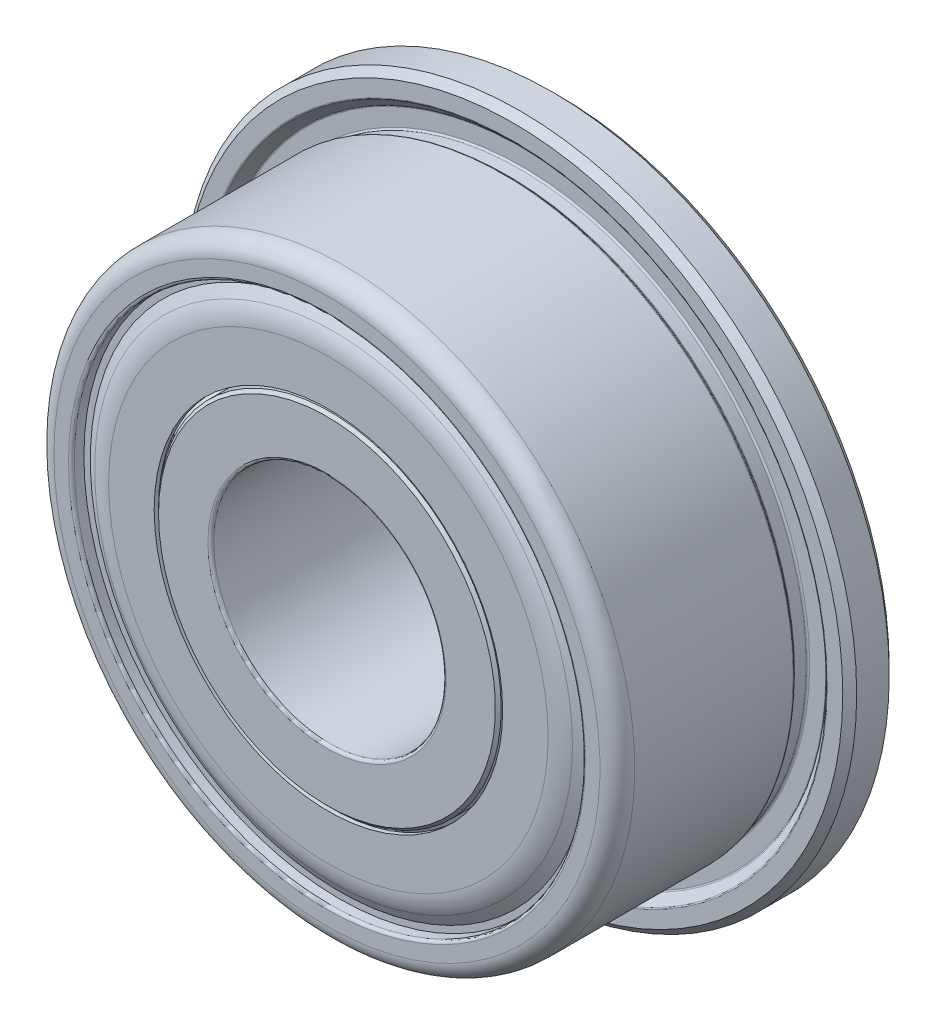
SolidWorks part; units mm, degrees
note: '?' marks a value the reader was unsure of.
ref_plane "Front Plane" through (0, 0, 0) normal (0, 0, 1) x (1, 0, 0)
ref_plane "Top Plane" through (0, 0, 0) normal (0, 1, 0) x (1, 0, 0)
ref_plane "Right Plane" through (0, 0, 0) normal (1, 0, 0) x (0, 0, -1)
sketch "Sketch1" plane through (0, 0, 0) normal (1, 0, 0) x (0, 0, -1)
  line L0 (-2, 0) -> (2, 0) construction
  line L1 (0, 5) -> (0, -5) construction
  line L2 (2, 5) -> (-2, 5)
  line L4 (-2, 5) -> (-2, 4.4)
  line L5 (-2, 4.4) -> (-0.78, 4.4)
  line L6 (2, 4.4) -> (0.78, 4.4)
  line L7 (2, 5) -> (2, 4.4)
  line L9 (0, 5) -> (0, 3.5) construction
  line L10 (0, 3.5) -> (0, 2) construction
  line L11 (-2, -4.4) -> (-2, 4.4) construction
  line L12 (1.2, -5.8) -> (2, -5.8)
  line L13 (1.2, -5.8) -> (1.2, 5.8)
  line L14 (1.2, 5.8) -> (2, 5.8)
  line L15 (2, -5.8) -> (2, 5.8)
  line L16 (1.2, -5.8) -> (2, 5.8) construction
  line L17 (1.2, 5.8) -> (2, -5.8) construction
  line L18 (-2, -2.95) -> (-2, 2.95)
  line L24 (0, -5) -> (-2, -5)
  line L25 (0, 2) -> (0, 5) construction
  line L26 (-2, 2.95) -> (-2, 2)
  line L27 (-2, 2) -> (2, 2)
  line L28 (2, 2) -> (2, 2.95)
  line L29 (2, 2.95) -> (0.58, 2.95)
  line L30 (-2, 2.95) -> (-0.58, 2.95)
  line L31 (-0.78, 4.4) -> (-0.78, 4.11)
  line L32 (-0.78, 4.11) -> (-0.58, 4.11)
  line L33 (0.78, 4.4) -> (0.78, 4.11)
  line L34 (0.78, 4.11) -> (0.58, 4.11)
  arc A3 (-0.58, 2.95) -> (0.58, 2.95) centre (0, 3.5) ccw
  circle A5 centre (0, 3.5247) radius 0.794
  arc A6 (-0.58, 4.11) -> (0.58, 4.11) centre (0, 3.5247) cw
  point P7 (-2, 4.4)
  point P13 (-1.9, 4.4)
  point P14 (0, 2)
  point P15 (1.6, 0)
  point P22 (2, 0)
  point P25 (-2, 0)
  point P27 (-2, 0)
  point P28 (-1.8, 4.4)
  point P29 (-1.7, 4.4)
  point P30 (-1.6, 4.4)
  point P31 (-1.5, 4.4)
  point P32 (-1.4, 4.4)
  point P33 (-1.3, 4.4)
  point P46 (0, 4.3487)
  point P50 (0, 2.7007)
  point P51 (0, 2.7307)
  point P52 (0, 4.3187)
  dimension "D3" = 1.588
  dimension "Shaft Dia" = 4
  dimension "Flange Thickness" = 0.8
  dimension "Flange OD" = 11.6
  dimension "D11" = 8.8
  dimension "D10" = 5.9
  dimension "Width" = 4
  dimension "OD" = 10
  dimension "D4" = 0.03
  dimension "D2" = 0.03
  dimension "D5" = 0.2
  dimension "D6" = 0.1
  dimension "D7" = 1.16
  dimension "D1" = 8
sketch "Sketch2" plane through (0, 0, 0) normal (0, 0, 1) x (1, 0, 0)
  line L0 (0, -2.95) -> (0, 2.95) construction
  circle A0 centre (0, 0) radius 2
  dimension "D1" = 4
sketch "Sketch3" plane through (0, 0, 0) normal (1, 0, 0) x (0, 0, -1)
  line L2 (-2, 5) -> (-2, 4.4) construction
  line L3 (2, 5) -> (-2, 5) construction
  line L4 (2, 5) -> (2, 4.4) construction
  line L5 (2, 4.4) -> (0.78, 4.4) construction
  line L6 (-2, 4.4) -> (-0.78, 4.4) construction
  line L13 (-2, 5) -> (-2, 4.4)
  line L21 (2, 5) -> (-2, 5)
  line L22 (2, 5) -> (2, 4.4)
  line L23 (2, 4.4) -> (0.78, 4.4)
  line L24 (-2, 4.4) -> (-0.78, 4.4)
  line L25 (2, 2) -> (-2, 2)
  line L27 (-2, 2) -> (-2, 2.95)
  line L28 (-2, 2.95) -> (-0.58, 2.95)
  line L29 (0.78, 4.4) -> (0.78, 4.11) construction
  line L30 (2, 2) -> (2, 2.95)
  line L31 (2, -5.8) -> (2, 5.8) construction
  line L32 (2, 2.95) -> (0.58, 2.95)
  line L33 (0.78, 4.11) -> (0.58, 4.11) construction
  line L34 (-0.78, 4.11) -> (-0.58, 4.11) construction
  line L35 (-0.78, 4.4) -> (-0.78, 4.11) construction
  line L36 (0.78, 4.4) -> (0.78, 4.11)
  line L37 (0.78, 4.11) -> (0.58, 4.11)
  line L38 (-0.78, 4.11) -> (-0.58, 4.11)
  line L39 (-0.78, 4.4) -> (-0.78, 4.11)
  arc A4 (0.58, 4.11) -> (-0.58, 4.11) centre (0, 3.5247) ccw construction
  arc A5 (-0.58, 2.95) -> (0.58, 2.95) centre (0, 3.5) ccw construction
  arc A6 (-0.58, 2.95) -> (0.58, 2.95) centre (0, 3.5) ccw
  arc A7 (0.58, 4.11) -> (-0.58, 4.11) centre (0, 3.5247) ccw
  point P15 (0, 2)
revolve "Revolve1" add sketch "Sketch3" angle 360 about L0
sketch "Sketch5" plane through (0, 0, 0) normal (1, 0, 0) x (0, 0, -1)
  line L0 (-0.794, 3.5247) -> (0.794, 3.5247)
  line L1 (0, 5) -> (0, -5) construction
  circle A0 centre (0, 3.5247) radius 0.794 construction
  arc A1 (-0.794, 3.5247) -> (0.794, 3.5247) centre (0, 3.5247) cw
revolve "Revolve3" add sketch "Sketch5" angle 360 about L0
ref_axis "Axis1" through (0, 0, -2) along (0, 0, 1)?
pattern_circular "CirPattern1" count 8 over 360 about axis through (0, 0, 0) along (0, 0, 1) of bodies 122
sketch "Sketch6" plane through (0, 0, 0) normal (1, 0, 0) x (0, 0, -1)
  line L1 (-1.975, 2.95) -> (-1.975, 3.7832)
  line L2 (-1.8866, 4.1132) -> (-1.7845, 4.29)
  line L4 (-1.7845, 4.29) -> (-1.6979, 4.29) construction
  line L5 (-1.7845, 4.29) -> (-1.7845, 4.4)
  line L6 (-1.7845, 4.4) -> (-1.6979, 4.4)
  line L7 (-1.6979, 4.29) -> (-1.9, 3.9399)
  line L8 (-1.9, 3.9399) -> (-1.9, 2.95)
  line L9 (-1.9, 2.95) -> (-1.975, 2.95)
  line L10 (0, 5) -> (0, -5) construction
  line L11 (-1.6979, 4.4) -> (-1.6979, 4.29)
  line L12 (-2, 4.4) -> (-0.78, 4.4) construction
  line L14 (0, 5) -> (0, 4.3487) construction
  arc A0 (-1.975, 3.7832) -> (-1.8866, 4.1132) centre (-1.315, 3.7832) cw
  point P22 (-1.975, 3.96)
  dimension "D8" = 0.66
  dimension "D1" = 30
  dimension "D3" = 0.075
  dimension "D2" = 0.025
  dimension "D4" = 0.075
  dimension "D6" = 0.33
  dimension "D5" = 1.45
  dimension "D7" = 0.11
revolve "Revolve4" add sketch "Sketch6" angle 360 about L0
mirror "Mirror1" about plane through (0, 0, 0) normal (0, 0, 1) of bodies 138
sketch "Sketch9" plane through (0, 0, 1.975) normal (0, 0, 1) x (1, 0, 0)
  circle A2 centre (0, 0) radius 3
  circle A3 centre (0, 0) radius 3
  dimension "D1" = 0.05
extrude "Cut-Extrude1" cut sketch "Sketch9" against normal through all
sketch "Sketch7" plane through (0, 0, 0) normal (1, 0, 0) x (0, 0, -1)
  line L0 (2, 0) -> (-2, 0) construction
  line L2 (1.2, 5.8) -> (2, 5.8)
  line L3 (1.2, 5.8) -> (1.2, 4.4)
  line L4 (1.2, 4.4) -> (2, 4.4)
  line L5 (2, 5.8) -> (2, 4.4)
revolve "Revolve5" add sketch "Sketch7" angle 360 about L0
fillet "Fillet2" radius 0.3 1 edges at (5, 0, 2)
fillet "Fillet3" radius 0.05 4 edges at (4.4, 0, -0.78) (4.4, 0, -2) (4.4, 0, 2) (4.4, 0, 0.78)
fillet "Fillet6" radius 0.05 4 edges at (2.95, 0, -2) (2.95, 0, -0.58) (2.95, 0, 0.58) (2.95, 0, 2)
sketch "Sketch8" plane through (0, 0, 0) normal (1, 0, 0) x (0, 0, -1)
  line L7 (1.2, 5.8) -> (1.2, 5) construction
  line L8 (1.2, 5.4) -> (1.36, 5.24)
  line L9 (1.36, 5.24) -> (1.36, 4.92)
  line L10 (1.36, 4.92) -> (1.12, 4.92)
  line L11 (1.12, 4.92) -> (1.04, 5)
  line L12 (1.2, 5) -> (-1.7, 5) construction
  line L13 (1.04, 5) -> (1.2, 5)
  line L14 (1.2, 5) -> (1.2, 5.4)
  dimension "D1" = 45
  dimension "D2" = 45
  dimension "D3" = 0.16
  dimension "D4" = 0.08
  dimension "D5" = 0.08
revolve "Cut-Revolve1" cut sketch "Sketch8" angle 360 about L0
fillet "Fillet5" radius 0.03 5 edges at (5, 0, -1.04) (4.92, 0, -1.12) (4.92, 0, -1.36) (5.24, 0, -1.36) (5.4, 0, -1.2)
chamfer "Chamfer1" distance 0.12 angle 45 2 edges at (-5.8, 0, -2) (-5.8, 0, -1.2)
fillet "Fillet7" radius 0.05 2 edges at (2, 0, 2) (2, 0, -2)
other "Save Bodies2"
equation "\"Balls@CirPattern1\"=\"D1@Sketch1\""
equation "\"D3@Sketch8\" = \"Flange Thickness@Sketch1\" * .2"
equation "\"D4@Sketch8\" = \"D3@Sketch8\" * .5"
equation "\"D5@Sketch8\" = \"D3@Sketch8\" * .5"
equation "\"D1@Chamfer1\"=\"Flange Thickness@Sketch1\"*.15"
equation "\"D1@Fillet6\"=\"D1@Fillet3\""
equation "\"D4@Sketch1\"=\"D2@Sketch1\""
equation "\"D7@Sketch1\" =  ( \"D11@Sketch1\" - \"D10@Sketch1\" )  * .40"
equation "\"D3@Sketch6\"=\"D4@Sketch6\""
equation "\"D8@Sketch6\"=\"D6@Sketch6\"*2"
